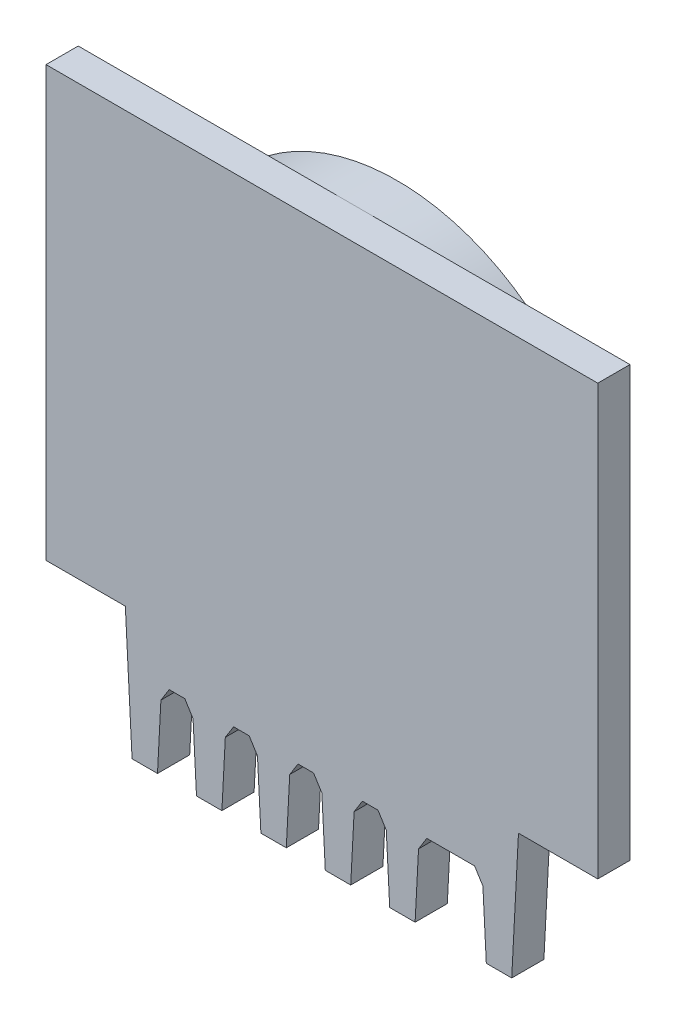
SolidWorks part; units mm, degrees
ref_plane "Front Plane" through (0, 0, 0) normal (0, 0, 1) x (1, 0, 0)
ref_plane "Top Plane" through (0, 0, 0) normal (0, 1, 0) x (1, 0, 0)
ref_plane "Right Plane" through (0, 0, 0) normal (1, 0, 0) x (0, 0, -1)
sketch "Sketch1" plane through (0, 0, 0) normal (0, 0, 1) x (1, 0, 0)
  line L0 (0, 0) -> (0, 26) construction
  line L1 (0, 26) -> (18.3124, 26) construction
  line L2 (18.3124, 26) -> (18.3124, 0) construction
  line L3 (18.3124, 0) -> (0, 0) construction
  line L4 (0, 3) -> (18.3124, 3) construction
  line L5 (0, 6) -> (18.3124, 6) construction
  line L6 (0.9062, 6) -> (0.9062, 0) construction
  line L7 (3.9062, 6) -> (3.9062, 0) construction
  line L8 (6.9062, 6) -> (6.9062, 0) construction
  line L9 (9.9062, 6) -> (9.9062, 0) construction
  line L10 (12.9062, 6) -> (12.9062, 0) construction
  line L11 (17.4062, 6) -> (17.4062, 0) construction
  line L12 (0.9062, 3) -> (3.9062, 3) construction
  line L13 (3.9062, 3) -> (6.9062, 3) construction
  line L14 (6.9062, 3) -> (9.9062, 3) construction
  line L15 (9.9062, 3) -> (12.9062, 3) construction
  line L16 (12.9062, 3) -> (17.4062, 3) construction
  line L17 (0.9062, 3) -> (0, 3) construction
  line L18 (17.4062, 3) -> (18.3124, 3) construction
  line L19 (2.4062, 3) -> (2.4062, 0) construction
  line L20 (5.4062, 3) -> (5.4062, 0) construction
  line L21 (8.4062, 3) -> (8.4062, 0) construction
  line L22 (11.4062, 3) -> (11.4062, 0) construction
  line L23 (15.1562, 3) -> (15.1562, 0) construction
  line L24 (14.4062, 3.75) -> (15.9062, 3.75) construction
  line L25 (0, 6) -> (0.3144, 0)
  line L26 (0.3144, 0) -> (1.4979, 0)
  line L27 (1.4979, 0) -> (1.6572, 3.0393)
  line L28 (3.1552, 3.0393) -> (3.3144, 0)
  line L29 (3.3144, 0) -> (4.4979, 0)
  line L30 (4.4979, 0) -> (4.6572, 3.0393)
  line L31 (6.1552, 3.0393) -> (6.3144, 0)
  line L32 (6.3144, 0) -> (7.4979, 0)
  line L33 (7.4979, 0) -> (7.6572, 3.0393)
  line L34 (9.1552, 3.0393) -> (9.3144, 0)
  line L35 (9.3144, 0) -> (10.4979, 0)
  line L36 (10.4979, 0) -> (10.6572, 3.0393)
  line L37 (12.1552, 3.0393) -> (12.3144, 0)
  line L38 (12.3144, 0) -> (13.4979, 0)
  line L39 (13.4979, 0) -> (13.6572, 3.0393)
  line L40 (16.6552, 3.0393) -> (16.8144, 0)
  line L41 (16.8144, 0) -> (17.9979, 0)
  line L42 (17.9979, 0) -> (18.3124, 6)
  line L44 (1.6572, 3.0393) -> (2.0426, 3.656)
  line L45 (0, 6) -> (-3.6938, 6)
  line L46 (-3.6938, 26) -> (22.0062, 26)
  line L47 (-3.6938, 6) -> (-3.6938, 26)
  line L48 (9.1562, 26) -> (9.1562, 6) construction
  line L49 (2.0426, 3.656) -> (2.7698, 3.656)
  line L50 (2.7698, 3.656) -> (3.1552, 3.0393)
  line L51 (4.6572, 3.0393) -> (5.0426, 3.656)
  line L52 (5.0426, 3.656) -> (5.7698, 3.656)
  line L53 (5.7698, 3.656) -> (6.1552, 3.0393)
  line L54 (7.6572, 3.0393) -> (8.0426, 3.656)
  line L55 (8.0426, 3.656) -> (8.7698, 3.656)
  line L56 (8.7698, 3.656) -> (9.1552, 3.0393)
  line L57 (10.6572, 3.0393) -> (11.0426, 3.656)
  line L58 (11.0426, 3.656) -> (11.7698, 3.656)
  line L59 (11.7698, 3.656) -> (12.1552, 3.0393)
  line L60 (13.6572, 3.0393) -> (14.0426, 3.656)
  line L61 (14.0426, 3.656) -> (16.2698, 3.656)
  line L62 (16.2698, 3.656) -> (16.6552, 3.0393)
  line L63 (18.3124, 6) -> (22.0062, 6)
  line L64 (22.0062, 6) -> (22.0062, 26)
  arc A0 (3.1552, 3.0393) -> (1.6572, 3.0393) centre (2.4062, 3) ccw construction
  arc A1 (6.1552, 3.0393) -> (4.6572, 3.0393) centre (5.4062, 3) ccw construction
  arc A2 (9.1552, 3.0393) -> (7.6572, 3.0393) centre (8.4062, 3) ccw construction
  arc A3 (12.1552, 3.0393) -> (10.6572, 3.0393) centre (11.4062, 3) ccw construction
  arc A4 (13.6572, 3.0393) -> (14.4062, 3.75) centre (14.4062, 3) cw construction
  arc A5 (16.6552, 3.0393) -> (15.9062, 3.75) centre (15.9062, 3) ccw construction
  circle A7 centre (9.1562, 16) radius 10 construction
  dimension "D7" = 0.75
  dimension "D11" = 20
  dimension "D1" = 3
  dimension "D2" = 6
  dimension "D4" = 3
  dimension "D5" = 25.7
  dimension "D6" = 4.5
  dimension "D8" = 3
  dimension "D9" = 18.3124
  dimension "D10" = 26
extrude "Boss-Extrude1" add sketch "Sketch1" along normal blind 1.5
sketch "Sketch3" plane through (0, 0, 0) normal (0, 0, 1) x (1, 0, 0)
  line L0 (-0.4005, 6) -> (18.7129, 6)
  line L1 (18.7129, 3) -> (-0.4005, 3) construction
  line L2 (-0.4005, 0) -> (18.7129, 0) construction
  line L3 (-0.4005, -0.5) -> (18.7129, -0.5) construction
  line L4 (18.7129, -0.5) -> (18.7129, 6) construction
  line L5 (-0.4005, 6) -> (-0.4005, -0.5) construction
  line L6 (18.3124, 0) -> (0, 0) construction
  line L7 (0, 3) -> (18.3124, 3) construction
  line L8 (0, 6) -> (18.3124, 6) construction
  line L9 (0.3407, -0.5) -> (0, 6) construction
  line L10 (18.3124, 6) -> (17.9717, -0.5) construction
  line L11 (17.9979, 0) -> (18.3124, 6) construction
  line L12 (0, 6) -> (0.3144, 0) construction
  line L13 (5.4062, 6) -> (5.4062, -0.5) construction
  line L14 (3.9062, 6) -> (3.9062, -0.5) construction
  line L15 (5.4062, 3) -> (5.4062, 0) construction
  line L16 (3.1572, 3) -> (3.3407, -0.5) construction
  line L17 (2.7567, 3) -> (2.9401, -0.5)
  line L18 (3.1552, 3.0393) -> (3.3144, 0) construction
  line L19 (2.9401, -0.5) -> (4.8723, -0.5)
  line L20 (4.8723, -0.5) -> (5.0557, 3)
  line L21 (2.8484, 1.25) -> (3.2478, 1.2709) construction
  line L22 (5.9401, -0.5) -> (5.7567, 3)
  line L26 (7.8723, -0.5) -> (5.9401, -0.5)
  line L27 (8.0557, 3) -> (7.8723, -0.5)
  line L30 (2.4062, -0.5) -> (2.4062, 6) construction
  line L31 (2.4062, 3) -> (2.4062, 0) construction
  line L32 (8.4062, 6) -> (8.4062, -0.5) construction
  line L34 (11.4062, -0.5) -> (11.4062, 6) construction
  line L35 (15.1562, -0.5) -> (15.1562, 6) construction
  line L36 (8.4062, 3) -> (8.4062, 0) construction
  line L37 (11.4062, 3) -> (11.4062, 0) construction
  line L38 (15.1562, 3) -> (15.1562, 0) construction
  line L39 (10.8723, -0.5) -> (11.0557, 3)
  line L40 (8.9401, -0.5) -> (10.8723, -0.5)
  line L41 (8.7567, 3) -> (8.9401, -0.5)
  line L42 (11.9401, -0.5) -> (11.7567, 3)
  line L43 (13.8723, -0.5) -> (11.9401, -0.5)
  line L44 (14.0557, 3) -> (13.8723, -0.5)
  line L45 (16.4401, -0.5) -> (18.3723, -0.5)
  line L46 (16.2567, 3) -> (16.4401, -0.5)
  line L47 (18.3723, -0.5) -> (18.7129, 6)
  line L48 (1.8723, -0.5) -> (-0.0599, -0.5)
  line L49 (2.0557, 3) -> (1.8723, -0.5)
  line L50 (-0.0599, -0.5) -> (-0.4005, 6)
  line L51 (16.2567, 3) -> (14.0557, 3)
  line L52 (11.7567, 3) -> (11.0557, 3)
  line L53 (8.7567, 3) -> (8.0557, 3)
  line L54 (5.7567, 3) -> (5.0557, 3)
  line L55 (2.7567, 3) -> (2.0557, 3)
  dimension "D1" = 0.5
  dimension "D2" = 0.4
ref_plane "Plane1" through (3.9062, 0, 0) normal (1, 0, 0) x (0, 0, -1)
sketch "Sketch4" plane through (3.9062, 0, 0) normal (1, 0, 0) x (0, 0, -1)
  line L0 (0, 6) -> (0, -0.5) construction
  line L1 (0.6, 6) -> (-2.1, 6) construction
  line L2 (0.6, 6) -> (0.6, -0.5) construction
  line L3 (0.6, -0.5) -> (-2.1, -0.5) construction
  line L4 (-2.1, 6) -> (-2.1, -0.5) construction
  line L5 (-0.75, -0.5) -> (-0.75, 6) construction
  line L6 (-1.5, 6) -> (-1.5, -0.5) construction
  line L7 (0.6, 2.4005) -> (-2.1, 2.4005) construction
  line L8 (0.3, 6) -> (0.3, -0.5) construction
  line L9 (0.6, 2.4005) -> (3.846, 6) construction
  line L10 (2.2302, 6) -> (0.6, 4.1923) construction
  line L11 (0.6, 4.1923) -> (1.7139, 3.1878) construction
  line L12 (1.7139, 3.1878) -> (4.25, 6)
  line L13 (4.25, 6) -> (0.6, 6) construction
  line L14 (0.3, 1) -> (-1.8, 1) construction
  line L15 (-2.1, 0) -> (0.6, 0) construction
  line L16 (1.7139, 3.1878) -> (1.4912, 3.3887)
  line L17 (1.4912, 3.3887) -> (0.6, 2.4005)
  line L18 (-3.2139, 3.1878) -> (-5.75, 6)
  line L19 (-3.2139, 3.1878) -> (-2.9912, 3.3887)
  line L20 (-2.9912, 3.3887) -> (-2.1, 2.4005)
  line L21 (-2.1, 6) -> (-5.75, 6) construction
  line L22 (0.6, 3.0724) -> (3.2401, 6) construction
  arc A0 (0.4965, 2.2224) -> (0.6, -0.5) centre (4.2, 1) ccw
  arc A1 (0.6, 2.4005) -> (0.4965, 2.2224) centre (0.9713, 2.0656) ccw
  arc A2 (-2.1, 2.4005) -> (-1.9965, 2.2224) centre (-2.4713, 2.0656) cw
  arc A3 (-1.9965, 2.2224) -> (-2.1, -0.5) centre (-5.7, 1) cw
  dimension "D6" = 0.5
  dimension "D1" = 0.6
  dimension "D2" = 0.3
  dimension "D3" = 1.5
  dimension "D4" = 1
  dimension "D5" = 0.3
  dimension "D7" = 10
sketch "Sketch5" plane through (0, 0, 0) normal (1, 0, 0) x (0, 0, -1)
  line L0 (2.2302, 6) -> (0.6, 4.1923) construction
  line L1 (0.6, 4.1923) -> (1.7139, 3.1878) construction
  line L2 (1.7139, 3.1878) -> (4.25, 6) construction
  line L3 (2.2302, 6) -> (0.6, 4.1923) construction
  line L4 (0.6, 4.1923) -> (1.7139, 3.1878) construction
  line L5 (1.7139, 3.1878) -> (4.25, 6) construction
ref_plane "Plane2" through (0, 2.6105, -2.3541) normal (0, 0.7426, -0.6697) x (1, 0, 0)
sketch "Sketch6" plane through (0, 2.6105, -2.3541) normal (0, 0.7426, -0.6697) x (1, 0, 0)
  line L1 (3.9062, -2.362) -> (3.9062, -0.862) construction
  line L2 (3.9062, -2.362) -> (3.9062, -5.0612) construction
  line L3 (4.6562, -5.0612) -> (3.1562, -5.0612)
  line L4 (4.6562, -1.612) -> (3.1562, -1.612) construction
  line L5 (3.1562, -1.612) -> (3.1562, -5.0612)
  line L6 (4.6562, -1.612) -> (4.6562, -5.0612)
  line L10 (2.4062, -5.0612) -> (15.1562, -5.0612) construction
  line L11 (15.1562, -5.0612) -> (15.1562, -0.862) construction
  line L12 (15.1562, -0.862) -> (2.4062, -0.862) construction
  line L13 (2.4062, -0.862) -> (2.4062, -5.0612) construction
  line L14 (15.1562, 0.3349) -> (15.1562, -4.0182) construction
  line L15 (2.4062, 0.3349) -> (2.4062, -4.0182) construction
  line L16 (11.4062, -5.0612) -> (11.4062, -0.862) construction
  line L17 (8.4062, -5.0612) -> (8.4062, -0.862) construction
  line L18 (5.4062, -5.0612) -> (5.4062, -0.862) construction
  line L19 (5.4062, -4.0182) -> (5.4062, 0.3349) construction
  line L20 (8.4062, -4.0182) -> (8.4062, 0.3349) construction
  line L21 (11.4062, 0.3349) -> (11.4062, -4.0182) construction
  line L22 (0.1562, -1.612) -> (0.1562, -5.0612)
  line L23 (0.1562, -5.0612) -> (1.6562, -5.0612)
  line L24 (1.6562, -1.612) -> (1.6562, -5.0612)
  line L25 (7.6562, -1.612) -> (7.6562, -5.0612)
  line L26 (6.1562, -5.0612) -> (7.6562, -5.0612)
  line L27 (6.1562, -1.612) -> (6.1562, -5.0612)
  line L28 (10.6562, -1.612) -> (10.6562, -5.0612)
  line L29 (10.6562, -5.0612) -> (9.1562, -5.0612)
  line L30 (9.1562, -1.612) -> (9.1562, -5.0612)
  line L31 (13.6562, -1.612) -> (13.6562, -5.0612)
  line L32 (12.1562, -5.0612) -> (13.6562, -5.0612)
  line L33 (12.1562, -1.612) -> (12.1562, -5.0612)
  line L34 (18.1562, -1.612) -> (18.1562, -5.0612)
  line L35 (18.1562, -5.0612) -> (16.6562, -5.0612)
  line L36 (16.6562, -1.612) -> (16.6562, -5.0612)
  circle A0 centre (3.9062, -1.612) radius 0.75 construction
  arc A1 (4.6562, -1.612) -> (3.1562, -1.612) centre (3.9062, -1.612) ccw
  arc A2 (0.1562, -1.612) -> (1.6562, -1.612) centre (0.9062, -1.612) cw
  arc A3 (6.1562, -1.612) -> (7.6562, -1.612) centre (6.9062, -1.612) cw
  arc A4 (10.6562, -1.612) -> (9.1562, -1.612) centre (9.9062, -1.612) ccw
  arc A5 (12.1562, -1.612) -> (13.6562, -1.612) centre (12.9062, -1.612) cw
  arc A6 (18.1562, -1.612) -> (16.6562, -1.612) centre (17.4062, -1.612) ccw
ref_plane "Plane3" through (0, 1.6223, -1.463) normal (0, 0.7426, -0.6697) x (1, 0, 0)
sketch "Sketch7" plane through (0, 1.6223, -1.463) normal (0, 0.7426, -0.6697) x (1, 0, 0)
  line L0 (3.1562, -1.612) -> (3.1562, -5.0612) construction
  line L1 (4.6562, -5.0612) -> (3.1562, -5.0612) construction
  line L2 (4.6562, -1.612) -> (4.6562, -5.0612) construction
  line L3 (3.1562, -1.612) -> (3.1562, -5.0612) construction
  line L4 (4.6562, -5.0612) -> (3.1562, -5.0612) construction
  line L5 (4.6562, -1.612) -> (4.6562, -5.0612) construction
  line L6 (3.9062, -0.862) -> (3.9062, -5.0612) construction
  line L7 (4.6562, -1.612) -> (3.1562, -1.612) construction
  line L8 (4.6562, -2.362) -> (3.1562, -2.362) construction
  line L9 (3.4562, -1.612) -> (3.4562, -2.362)
  line L10 (3.4562, -2.362) -> (4.3562, -2.362)
  line L11 (4.3562, -2.362) -> (4.3562, -1.612)
  line L12 (2.4062, -0.862) -> (2.4062, -5.0612) construction
  line L13 (2.4062, -5.0612) -> (15.1562, -5.0612) construction
  line L14 (15.1562, -0.862) -> (2.4062, -0.862) construction
  line L15 (5.4062, -5.0612) -> (5.4062, -0.862) construction
  line L16 (8.4062, -5.0612) -> (8.4062, -0.862) construction
  line L17 (11.4062, -5.0612) -> (11.4062, -0.862) construction
  line L18 (15.1562, -5.0612) -> (15.1562, -0.862) construction
  line L19 (2.4062, -0.862) -> (2.4062, -5.0612) construction
  line L20 (2.4062, -5.0612) -> (15.1562, -5.0612) construction
  line L21 (15.1562, -0.862) -> (2.4062, -0.862) construction
  line L22 (5.4062, -5.0612) -> (5.4062, -0.862) construction
  line L23 (8.4062, -5.0612) -> (8.4062, -0.862) construction
  line L24 (11.4062, -5.0612) -> (11.4062, -0.862) construction
  line L25 (15.1562, -5.0612) -> (15.1562, -0.862) construction
  line L26 (0.4562, -2.362) -> (0.4562, -1.612)
  line L27 (1.3562, -2.362) -> (0.4562, -2.362)
  line L28 (1.3562, -1.612) -> (1.3562, -2.362)
  line L29 (7.3562, -2.362) -> (6.4562, -2.362)
  line L30 (7.3562, -1.612) -> (7.3562, -2.362)
  line L31 (6.4562, -2.362) -> (6.4562, -1.612)
  line L32 (9.4562, -1.612) -> (9.4562, -2.362)
  line L33 (10.3562, -2.362) -> (10.3562, -1.612)
  line L34 (9.4562, -2.362) -> (10.3562, -2.362)
  line L35 (13.3562, -1.612) -> (13.3562, -2.362)
  line L36 (12.4562, -2.362) -> (12.4562, -1.612)
  line L37 (13.3562, -2.362) -> (12.4562, -2.362)
  line L38 (16.9562, -1.612) -> (16.9562, -2.362)
  line L39 (17.8562, -2.362) -> (17.8562, -1.612)
  line L40 (16.9562, -2.362) -> (17.8562, -2.362)
  arc A0 (4.6562, -1.612) -> (3.1562, -1.612) centre (3.9062, -1.612) ccw construction
  arc A1 (4.6562, -1.612) -> (3.1562, -1.612) centre (3.9062, -1.612) ccw construction
  circle A2 centre (3.9062, -1.612) radius 0.45 construction
  arc A3 (4.3562, -1.612) -> (3.4562, -1.612) centre (3.9062, -1.612) ccw
  arc A4 (0.4562, -1.612) -> (1.3562, -1.612) centre (0.9062, -1.612) cw
  arc A5 (6.4562, -1.612) -> (7.3562, -1.612) centre (6.9062, -1.612) cw
  arc A6 (10.3562, -1.612) -> (9.4562, -1.612) centre (9.9062, -1.612) ccw
  arc A7 (12.4562, -1.612) -> (13.3562, -1.612) centre (12.9062, -1.612) cw
  arc A8 (17.8562, -1.612) -> (16.9562, -1.612) centre (17.4062, -1.612) ccw
ref_plane "bisect" through (0, 0, 0.75) normal (0, 0, 1) x (1, 0, 0)
ref_plane "insert_surface" through (0, 6, 0) normal (0, 1, 0) x (1, 0, 0)
sketch "Sketch8" plane through (0, 6, 0) normal (0, 1, 0) x (1, 0, 0)
  line L0 (18.7129, -0.75) -> (-0.4005, -0.75) construction
  line L1 (-0.4005, 0.6) -> (18.7129, 0.6)
  line L2 (-0.4005, 0.6) -> (-0.4005, -2.1)
  line L3 (-0.4005, -2.1) -> (18.7129, -2.1)
  line L4 (18.7129, 0.6) -> (18.7129, -2.1)
  line L5 (9.1562, 0.6) -> (9.1562, -2.1) construction
  line L6 (0, 0) -> (18.3124, 0) construction
  line L7 (0, 0) -> (0, -1.5) construction
  line L8 (0, -1.5) -> (18.3124, -1.5) construction
  line L9 (18.3124, 0) -> (18.3124, -1.5) construction
  line L10 (18.7129, 0.3) -> (-0.4005, 0.3) construction
  line L11 (18.7129, -1.8) -> (-0.4005, -1.8) construction
sketch "Sketch9" plane through (0, 0, 0) normal (0, 0, 1) x (1, 0, 0)
  line L0 (18.3723, -0.5) -> (18.7129, 6) construction
  line L1 (-0.4005, 6) -> (18.7129, 6) construction
  line L2 (-0.0599, -0.5) -> (-0.4005, 6) construction
  line L3 (1.8723, -0.5) -> (-0.0599, -0.5) construction
  line L4 (2.0557, 3) -> (1.8723, -0.5) construction
  line L5 (2.7567, 3) -> (2.0557, 3) construction
  line L6 (2.7567, 3) -> (2.9401, -0.5) construction
  line L7 (2.9401, -0.5) -> (4.8723, -0.5) construction
  line L8 (4.8723, -0.5) -> (5.0557, 3) construction
  line L9 (5.7567, 3) -> (5.0557, 3) construction
  line L10 (5.9401, -0.5) -> (5.7567, 3) construction
  line L11 (7.8723, -0.5) -> (5.9401, -0.5) construction
  line L12 (8.0557, 3) -> (7.8723, -0.5) construction
  line L13 (8.7567, 3) -> (8.0557, 3) construction
  line L14 (8.7567, 3) -> (8.9401, -0.5) construction
  line L15 (8.9401, -0.5) -> (10.8723, -0.5) construction
  line L16 (10.8723, -0.5) -> (11.0557, 3) construction
  line L17 (11.7567, 3) -> (11.0557, 3) construction
  line L18 (11.9401, -0.5) -> (11.7567, 3) construction
  line L19 (13.8723, -0.5) -> (11.9401, -0.5) construction
  line L20 (14.0557, 3) -> (13.8723, -0.5) construction
  line L21 (16.2567, 3) -> (14.0557, 3) construction
  line L22 (16.2567, 3) -> (16.4401, -0.5) construction
  line L23 (16.4401, -0.5) -> (18.3723, -0.5) construction
  line L24 (18.3723, -0.5) -> (18.7129, 6)
  line L25 (-0.4005, 6) -> (18.7129, 6) construction
  line L26 (-0.0599, -0.5) -> (-0.4005, 6)
  line L27 (1.8723, -0.5) -> (-0.0599, -0.5)
  line L28 (2.0557, 3) -> (1.8723, -0.5)
  line L29 (2.7567, 3) -> (2.0557, 3) construction
  line L30 (2.7567, 3) -> (2.9401, -0.5)
  line L31 (2.9401, -0.5) -> (4.8723, -0.5)
  line L32 (4.8723, -0.5) -> (5.0557, 3)
  line L33 (5.7567, 3) -> (5.0557, 3) construction
  line L34 (5.9401, -0.5) -> (5.7567, 3)
  line L35 (7.8723, -0.5) -> (5.9401, -0.5)
  line L36 (8.0557, 3) -> (7.8723, -0.5)
  line L37 (8.7567, 3) -> (8.0557, 3) construction
  line L38 (8.7567, 3) -> (8.9401, -0.5)
  line L39 (8.9401, -0.5) -> (10.8723, -0.5)
  line L40 (10.8723, -0.5) -> (11.0557, 3)
  line L41 (11.7567, 3) -> (11.0557, 3) construction
  line L42 (11.9401, -0.5) -> (11.7567, 3)
  line L43 (13.8723, -0.5) -> (11.9401, -0.5)
  line L44 (14.0557, 3) -> (13.8723, -0.5)
  line L45 (16.2567, 3) -> (14.0557, 3) construction
  line L46 (16.2567, 3) -> (16.4401, -0.5)
  line L47 (16.4401, -0.5) -> (18.3723, -0.5)
  line L48 (16.2567, 3) -> (16.2567, 6)
  line L49 (14.0557, 3) -> (14.0557, 6)
  line L50 (11.7567, 3) -> (11.7567, 6)
  line L51 (18.7129, 6) -> (-0.4005, 6) construction
  line L52 (11.0557, 3) -> (11.0557, 6)
  line L53 (-0.4005, 6) -> (18.7129, 6) construction
  line L54 (8.7567, 3) -> (8.7567, 6)
  line L55 (8.0557, 3) -> (8.0557, 6)
  line L58 (5.7567, 3) -> (5.7567, 6)
  line L60 (5.0557, 3) -> (5.0557, 6)
  line L62 (15.1562, -0.5) -> (15.1562, 6) construction
  line L63 (15.1562, -0.5) -> (15.1562, 6) construction
  line L64 (2.7567, 3) -> (2.7567, 6)
  line L65 (2.0557, 3) -> (2.0557, 6)
  line L67 (18.7129, 6) -> (16.2567, 6)
  line L68 (14.0557, 6) -> (11.7567, 6)
  line L69 (11.0557, 6) -> (8.7567, 6)
  line L70 (8.0557, 6) -> (5.7567, 6)
  line L71 (5.0557, 6) -> (2.7567, 6)
  line L72 (2.0557, 6) -> (-0.4005, 6)
sketch "Sketch10" plane through (0, 0, 0) normal (0, 0, 1) x (1, 0, 0)
  circle A0 centre (9.1562, 16) radius 10
extrude "Boss-Extrude2" add sketch "Sketch10" against normal blind 2
sketch "Sketch11" plane through (0, 6, 0) normal (0, 1, 0) x (1, 0, 0)
  line L0 (9.1562, 0) -> (9.1562, -5) construction
  line L1 (-0.8438, 5) -> (19.1562, 5)
  line L2 (-0.8438, 5) -> (-0.8438, -5)
  line L3 (-0.8438, -5) -> (19.1562, -5)
  line L4 (19.1562, 5) -> (19.1562, -5)
  line L5 (9.1562, 0) -> (9.1562, 5) construction
  line L6 (9.1562, 0) -> (19.1562, 0) construction
  line L7 (9.1562, 0) -> (-0.8438, 0) construction
  dimension "D1" = 10
  dimension "D2" = 20
